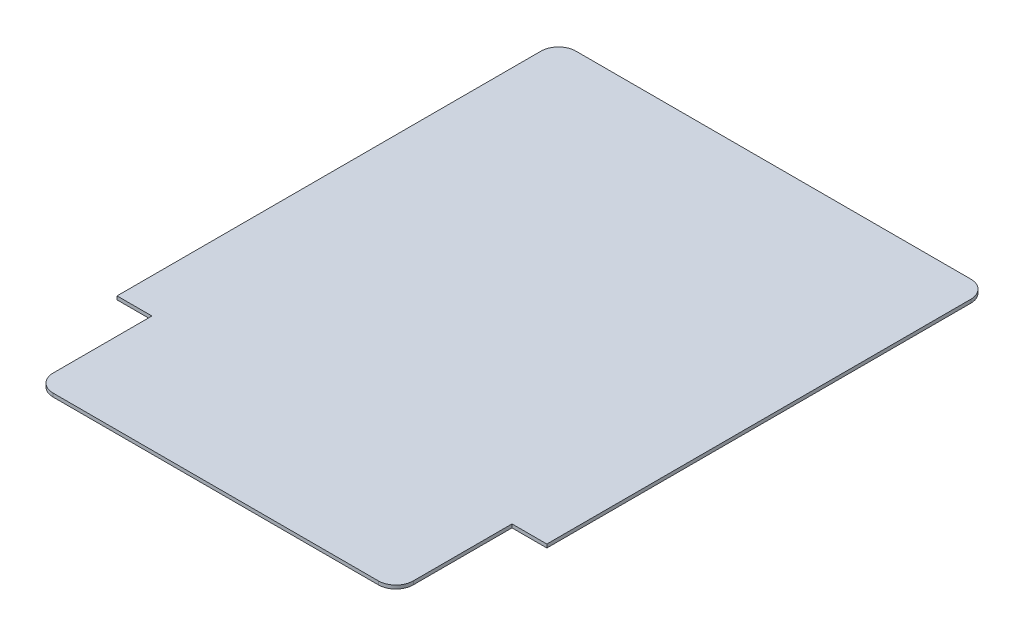
SolidWorks part; units mm, degrees
ref_plane "Front Plane" through (0, 0, 0) normal (0, 0, 1) x (1, 0, 0)
ref_plane "Top Plane" through (0, 0, 0) normal (0, 1, 0) x (1, 0, 0)
ref_plane "Right Plane" through (0, 0, 0) normal (1, 0, 0) x (0, 0, -1)
sketch "BaseSketch" plane through (0, 0, 0) normal (0, 1, 0) x (1, 0, 0)
  line L0 (209.55, 292.1) -> (222.25, 279.4) construction
  line L1 (-171.45, -292.1) -> (171.45, -292.1)
  line L2 (-222.25, -165.1) -> (-222.25, 292.1)
  line L3 (-222.25, 292.1) -> (222.25, 292.1)
  line L4 (222.25, -165.1) -> (222.25, 292.1)
  line L5 (-222.25, -292.1) -> (222.25, 292.1) construction
  line L6 (-222.25, 292.1) -> (222.25, -292.1) construction
  line L7 (222.25, -165.1) -> (171.45, -165.1)
  line L8 (171.45, -165.1) -> (171.45, -292.1)
  line L9 (171.45, -292.1) -> (-171.45, -292.1)
  line L10 (-171.45, -292.1) -> (-171.45, -165.1)
  line L11 (-171.45, -165.1) -> (-222.25, -165.1)
  line L12 (222.25, -165.1) -> (222.25, -292.1) construction
  line L13 (222.25, -292.1) -> (171.45, -292.1) construction
  line L14 (-171.45, -292.1) -> (-222.25, -292.1) construction
  line L15 (-222.25, -292.1) -> (-222.25, -165.1) construction
  line L16 (-222.25, 279.4) -> (-209.55, 292.1) construction
  line L17 (0, -2.0955) -> (0, 2.0955) construction
  point P0 (0, 0)
  dimension "D1" = 90
extrude "Boss-Extrude1" add sketch "BaseSketch" along normal blind 3.81 contours L11 L10 L1 L8 L7 L4 L3 L2 region at (0, 0, -11.9529)
sketch "Sketch7" plane through (0, 3.81, 0) normal (0, 1, 0) x (1, 0, 0)
  line L0 (-234.95, -177.8) -> (-196.85, -177.8)
  line L1 (-222.25, 292.1) -> (222.25, 292.1) construction
  line L2 (-222.25, -165.1) -> (-222.25, 292.1) construction
  line L3 (-171.45, -292.1) -> (171.45, -292.1) construction
  line L4 (222.25, -165.1) -> (222.25, 292.1) construction
  line L5 (-196.85, -177.8) -> (-196.85, -304.8)
  line L6 (-234.95, -177.8) -> (-234.95, -304.8) construction
  line L7 (-234.95, -304.8) -> (-196.85, -304.8) construction
  line L8 (196.85, -304.8) -> (196.85, -177.8)
  line L9 (196.85, -177.8) -> (234.95, -177.8)
  line L10 (234.95, -177.8) -> (234.95, -304.8) construction
  line L11 (234.95, -304.8) -> (196.85, -304.8) construction
  line L12 (234.95, -177.8) -> (234.95, 304.8)
  line L13 (234.95, 304.8) -> (-234.95, 304.8)
  line L14 (-234.95, 304.8) -> (-234.95, -177.8)
  line L15 (-196.85, -304.8) -> (196.85, -304.8)
  line L16 (-171.45, -165.1) -> (-222.25, -165.1) construction
  line L17 (-171.45, -292.1) -> (-171.45, -165.1) construction
  point P20 (-196.85, -165.1)
  dimension "D1" = 12.7
  dimension "D2" = 12.7
  dimension "D3" = 12.7
  dimension "D4" = 12.7
  dimension "D5" = 12.7
  dimension "D6" = 25.4
extrude "Boss-Extrude2" add sketch "Sketch7" against normal up to surface (3.81 mm away) up to face at (0, 0, 82.55)
fillet "Fillet1" radius 19.05 4 edges at (234.95, 1.905, -304.8) (-234.95, 1.905, -304.8) (196.85, 1.905, 304.8) (-196.85, 1.905, 304.8)
